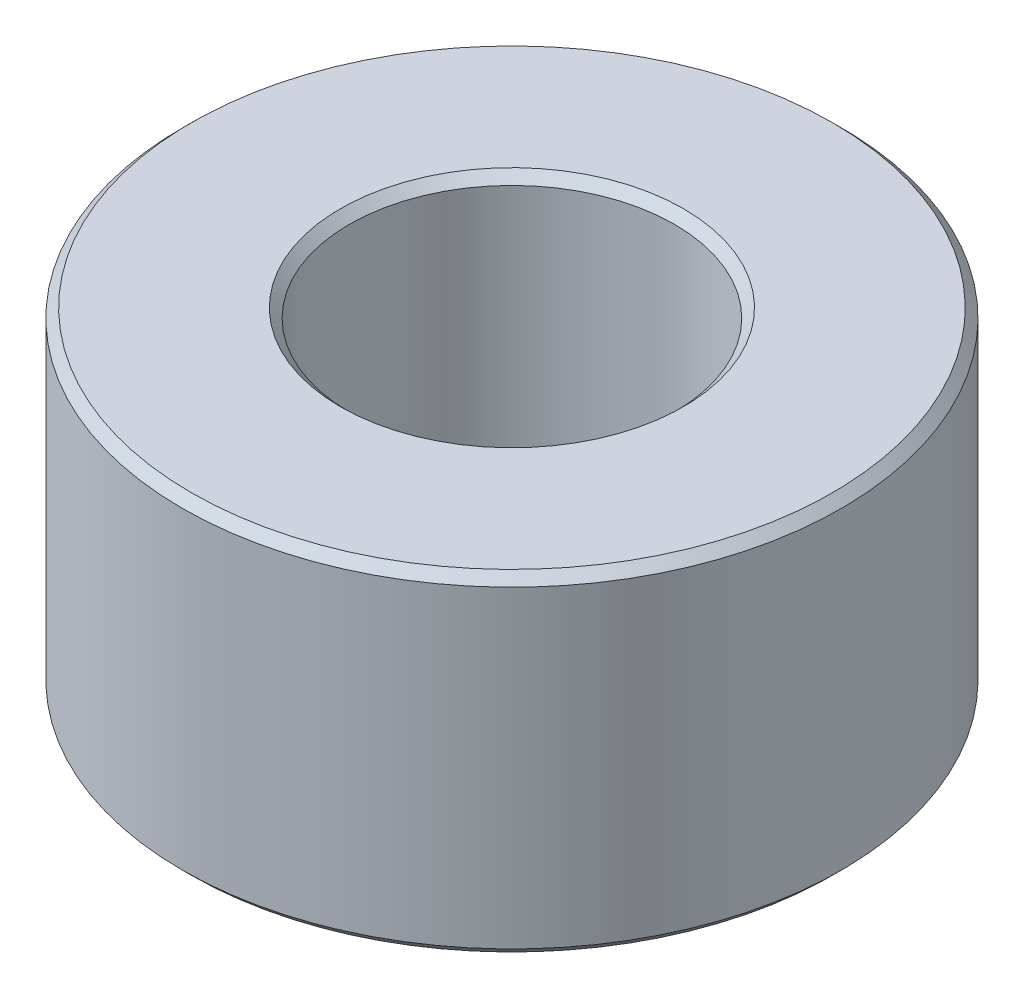
SolidWorks part; units mm, degrees
ref_plane "Front Plane" through (0, 0, 0) normal (0, 0, 1) x (1, 0, 0)
ref_plane "Top Plane" through (0, 0, 0) normal (0, 1, 0) x (1, 0, 0)
ref_plane "Right Plane" through (0, 0, 0) normal (1, 0, 0) x (0, 0, -1)
sketch "Sketch1" plane through (0, 0, 0) normal (0, 1, 0) x (1, 0, 0)
  circle A0 centre (0, 0) radius 25
  dimension "SLEEVE_OD" = 50
extrude "Boss-Extrude1" add sketch "Sketch1" along normal blind 25.1331
sketch "Sketch2" plane through (0, 0, 0) normal (0, 1, 0) x (1, 0, 0)
  circle A0 centre (0, 0) radius 12.3291
  dimension "BORE_D" = 24.6583
extrude "Cut-Extrude1" cut sketch "Sketch2" along normal through all
chamfer "Chamfer1" distance 0.6843 angle 45 4 edges at (0, 25.1331, 12.3291) (0, 0, 12.3291) (0, 0, 25) (0, 25.1331, 25)
